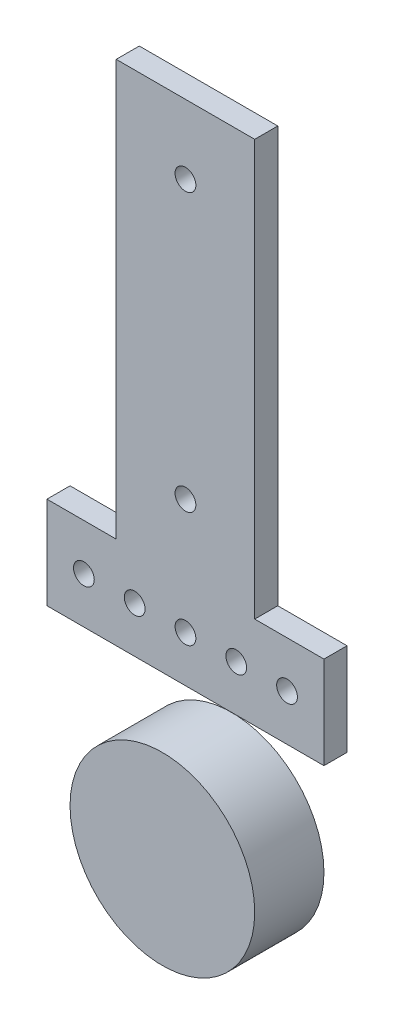
SolidWorks part; units mm, degrees
ref_plane "Front Plane" through (0, 0, 0) normal (0, 0, 1) x (1, 0, 0)
ref_plane "Top Plane" through (0, 0, 0) normal (0, 1, 0) x (1, 0, 0)
ref_plane "Right Plane" through (0, 0, 0) normal (1, 0, 0) x (0, 0, -1)
sketch "Sketch1" plane through (0, 0, 0) normal (0, 0, 1) x (1, 0, 0)
  line L0 (0, 60) -> (0, 0) construction
  line L1 (0, -15) -> (0, -35) construction
  line L2 (15, -15) -> (-15, -15)
  line L3 (15, -15) -> (15, 75)
  line L4 (15, 75) -> (-15, 75)
  line L5 (-15, -15) -> (-15, 75)
  line L6 (15, -15) -> (-15, 75) construction
  line L7 (15, 75) -> (-15, -15) construction
  line L12 (-30, -15) -> (30, -15)
  line L13 (-30, -15) -> (-30, -35)
  line L14 (-30, -35) -> (30, -35)
  line L15 (30, -15) -> (30, -35)
  circle A0 centre (0, 0) radius 2.25
  circle A1 centre (0, 60) radius 2.25
  circle A2 centre (0, -25) radius 2.25
  circle A3 centre (11, -25) radius 2.25
  circle A4 centre (22, -25) radius 2.25
  circle A5 centre (-11, -25) radius 2.25
  circle A6 centre (-22, -25) radius 2.25
  circle A7 centre (0, -65) radius 20
  point P4 (0, 30)
  point P10 (0, 75)
  point P14 (0, -15)
  point P16 (0, -15)
  point P18 (0, 0)
  point P31 (0, 0)
  point P32 (0, 0)
  dimension "D1" = 4.5
  dimension "D3" = 15
  dimension "D4" = 15
  dimension "D7" = 4.5
  dimension "D10" = 40
  dimension "D5" = 60
  dimension "D6" = 20
  dimension "D11" = 10
  dimension "D2" = 2
  dimension "D8" = 3
  dimension "D9" = 3
extrude "Boss-Extrude1" add sketch "Sketch1" along normal mid plane 5 contours L5 L2 L3 L4 A1 A0 | L15 L12 L2 L13 L14 A6 A5 A4 A3 A2 region at (22.5, -15.6325, 0) region at (0, 30, 0)
extrude "Boss-Extrude2" add sketch "Sketch1<3>" along normal mid plane 15 separate body contours A7 region at (0, -65, 0)
sketch "Sketch1<3>" plane through (0, 0, 0) normal (0, 0, 1) x (1, 0, 0) same geometry as "Sketch1"
